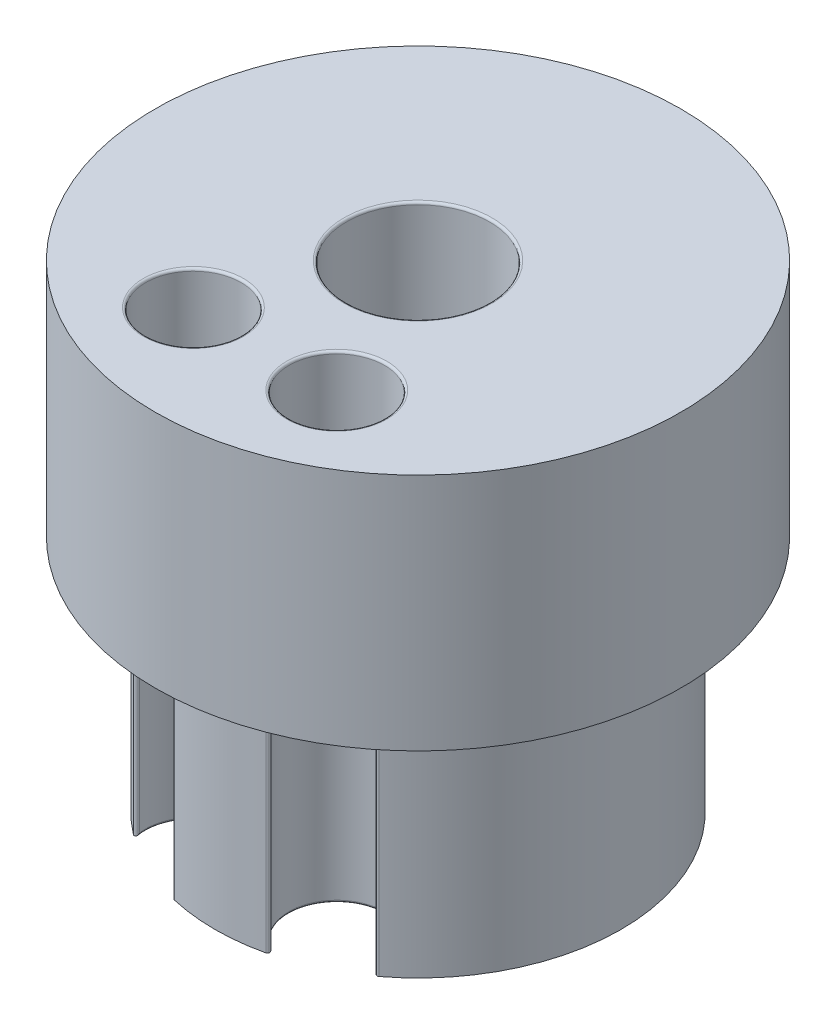
SolidWorks part; units mm, degrees
material "1060 Alloy"
ref_plane "Front Plane" through (0, 0, 0) normal (0, 0, 1) x (1, 0, 0)
ref_plane "Top Plane" through (0, 0, 0) normal (0, 1, 0) x (1, 0, 0)
ref_plane "Right Plane" through (0, 0, 0) normal (1, 0, 0) x (0, 0, -1)
sketch "Sketch1" plane through (0, 0, 0) normal (0, 1, 0) x (1, 0, 0)
  circle A0 centre (0, 0) radius 0.55
  dimension "D1" = 1.1
extrude "Boss-Extrude1" add sketch "Sketch1" against normal blind 0.5
sketch "Sketch2" plane through (0, -0.5, 0) normal (0, -1, 0) x (1, 0, 0)
  circle A0 centre (0, 0) radius 0.425
  dimension "D1" = 0.85
extrude "Boss-Extrude2" add sketch "Sketch2" along normal blind 0.5
sketch "Sketch3" plane through (0, 0, 0) normal (0, 1, 0) x (1, 0, 0)
  line L0 (0, 0) -> (0, -0.425) construction
  circle A0 centre (0, 0) radius 0.15
  circle A1 centre (0, 0) radius 0.425 construction
  circle A2 centre (0, 0) radius 0.425 construction
  circle A3 centre (0.15, -0.32) radius 0.1
  circle A4 centre (-0.15, -0.32) radius 0.1
  dimension "D1" = 0.3
  dimension "D4" = 0.32
  dimension "D5" = 0.2
  dimension "D2" = 0.15
  dimension "D3" = 0.15
extrude "Cut-Extrude1" cut sketch "Sketch3" against normal through all
fillet "Fillet5" radius 0.005 12 edges at (0, 0, 0.15) (0, -1, 0.15) (0.15, 0, 0.42) (0.1076, -1, 0.2295) (-0.15, 0, 0.42) (-0.1076, -1, 0.2295) (0.2465, -0.75, 0.3462) (0.1084, -0.75, 0.4109) (0.1924, -0.5, 0.4105) (-0.1084, -0.75, 0.4109) (-0.2465, -0.75, 0.3462) (-0.1924, -0.5, 0.4105)
ref_plane "Plane1" through (0, 0, 0.55) normal (0, 0, 1) x (1, 0, 0)
sketch "Sketch4" plane through (0, 0, 0.55) normal (0, 0, 1) x (1, 0, 0)
  line L0 (0, 0) -> (0, -1) construction
  line L1 (-0.0957, -1) -> (0.0957, -1) construction
